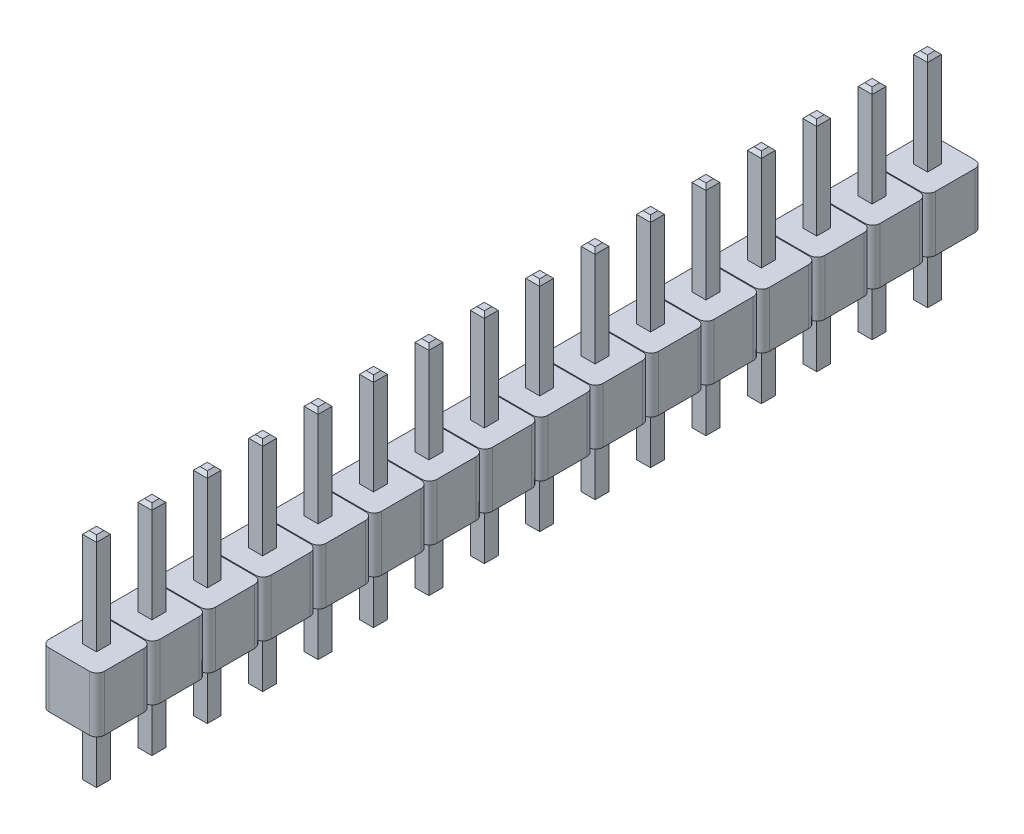
SolidWorks part; units mm, degrees
ref_plane "Front Plane" through (0, 0, 0) normal (0, 0, 1) x (1, 0, 0)
ref_plane "Top Plane" through (0, 0, 0) normal (0, 1, 0) x (1, 0, 0)
ref_plane "Right Plane" through (0, 0, 0) normal (1, 0, 0) x (0, 0, -1)
sketch "Sketch1" plane through (0, 0, 0) normal (0, 1, 0) x (1, 0, 0)
  line L1 (0, 0) -> (0.64, 0)
  line L2 (0, 0) -> (0, 0.64)
  line L3 (0, 0.64) -> (0.64, 0.64)
  line L4 (0.64, 0) -> (0.64, 0.64)
  dimension "D1" = 0.64
  dimension "D2" = 0.64
extrude "Boss-Extrude1" add sketch "Sketch1" along normal blind 10.04
chamfer "Chamfer1" distance 0.15 angle 45 8 edges at (0.32, 0, 0) (0.64, 0, -0.32) (0.32, 0, -0.64) (0, 0, -0.32) (0.32, 10.04, -0.64) (0.64, 10.04, -0.32) (0.32, 10.04, 0) (0, 10.04, -0.32)
ref_plane "Plane1" through (0, 5.54, 0) normal (0, 1, 0) x (1, 0, 0)
sketch "Sketch3" plane through (0, 5.54, 0) normal (0, 1, 0) x (1, 0, 0)
  line L0 (0.32, 0.64) -> (0.32, 0) construction
  line L1 (0, 0.64) -> (0.64, 0.64) construction
  line L2 (0.64, 0) -> (0, 0) construction
  line L4 (-0.6, -0.93) -> (1.24, -0.93)
  line L5 (-0.95, -0.58) -> (-0.95, 1.22)
  line L6 (-0.6, 1.57) -> (1.24, 1.57)
  line L7 (1.59, -0.58) -> (1.59, 1.22)
  line L8 (-0.95, -0.93) -> (1.59, 1.57) construction
  line L9 (-0.95, 1.57) -> (1.59, -0.93) construction
  arc A0 (-0.6, -0.93) -> (-0.95, -0.58) centre (-0.6, -0.58) cw
  arc A1 (1.24, 1.57) -> (1.59, 1.22) centre (1.24, 1.22) cw
  arc A2 (-0.95, 1.22) -> (-0.6, 1.57) centre (-0.6, 1.22) cw
  arc A3 (1.24, -0.93) -> (1.59, -0.58) centre (1.24, -0.58) ccw
  point P6 (0.32, 0.32)
  point P7 (0.32, 0.32)
  dimension "D3" = 0.35
  dimension "D1" = 2.5
  dimension "D2" = 2.54
extrude "Boss-Extrude2" add sketch "Sketch3" against normal blind 2.54
ref_axis "Axis1" through (0.32, 3, 0.93) along (0, 0, -1)
pattern_linear "LPattern2" count 16 spacing 2.54 along (0, 0, -1) of bodies 102
